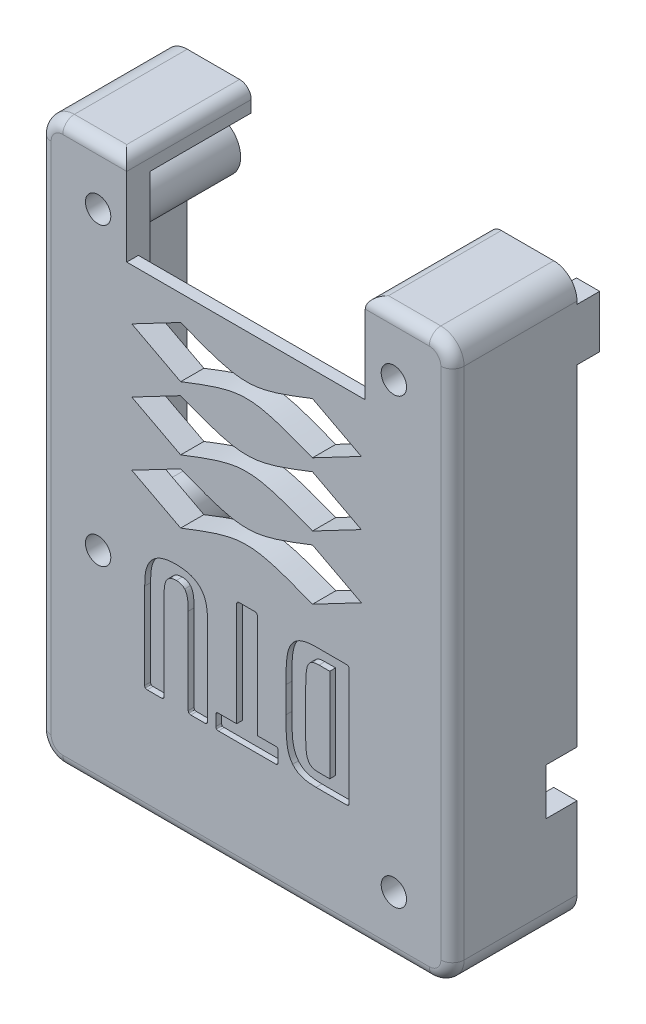
SolidWorks part; units mm, degrees
ref_plane "Front Plane" through (0, 0, 0) normal (0, 0, 1) x (1, 0, 0)
ref_plane "Top Plane" through (0, 0, 0) normal (0, 1, 0) x (1, 0, 0)
ref_plane "Right Plane" through (0, 0, 0) normal (1, 0, 0) x (0, 0, -1)
sketch "Sketch1" plane through (0, 0, 0) normal (0, 0, 1) x (1, 0, 0)
  line L1 (-7.3177, 13.3633) -> (23.1823, 13.3633)
  line L2 (-7.3177, 13.3633) -> (-7.3177, -29.8367)
  line L3 (-7.3177, -29.8367) -> (23.1823, -29.8367)
  line L4 (23.1823, 13.3633) -> (23.1823, -29.8367)
  line L5 (-7.8177, 13.8633) -> (23.6823, 13.8633)
  line L6 (-7.8177, 13.8633) -> (-7.8177, -30.3367)
  line L7 (-7.8177, -30.3367) -> (23.6823, -30.3367)
  line L8 (23.6823, 13.8633) -> (23.6823, -30.3367)
  line L9 (-9.8177, 15.8633) -> (25.6823, 15.8633)
  line L10 (-9.8177, 15.8633) -> (-9.8177, -32.3367)
  line L11 (-9.8177, -32.3367) -> (25.6823, -32.3367)
  line L12 (25.6823, 15.8633) -> (25.6823, -32.3367)
  circle A4 centre (20.6423, 10.8233) radius 1.09
  circle A6 centre (20.6423, -27.2967) radius 1.09
  circle A7 centre (-4.7777, -14.5767) radius 1.09
  circle A8 centre (-4.7777, 10.8233) radius 1.09
  dimension "D3" = 2.18
  dimension "D4" = 2.18
  dimension "D5" = 2.18
  dimension "D6" = 2.18
  dimension "D1" = 43.2
  dimension "D2" = 30.5
  dimension "D7" = 2.54
  dimension "D8" = 2.54
  dimension "D9" = 2.54
  dimension "D10" = 2.54
  dimension "D11" = 25.4
  dimension "D12" = 2.54
  dimension "D13" = 2.54
  dimension "D14" = 2.54
  dimension "D15" = 0.5
  dimension "D16" = 0.5
  dimension "D17" = 0.5
  dimension "D18" = 0.5
  dimension "D19" = 2
  dimension "D20" = 2
  dimension "D21" = 2
  dimension "D22" = 2
extrude "Boss-Extrude1" add sketch "Sketch1" along normal blind 10.7 contours A8 | A7 | A6 | L9 L12 L11 L10 | A4 region at (20.6423, -27.2967, 0) region at (-4.7777, -14.5767, 0) region at (-4.7777, 10.8233, 0)
extrude "Cut-Extrude1" cut sketch "Sketch1<6>" along normal blind 8.7 contours L6 L7 L8 L5
sketch "Sketch1<6>" plane through (0, 0, 0) normal (0, 0, 1) x (1, 0, 0) same geometry as "Sketch1"
sketch "Sketch3" plane through (-9.8177, -6.6544, 0) normal (-1, 0, 0) x (0, -1, 0)
  line L7 (-22.5177, 0) -> (25.6823, 0) construction
  line L8 (21.0823, 0) -> (10.0823, 0)
  line L9 (21.0823, 0) -> (21.0823, 4.2415)
  line L10 (21.0823, 4.2415) -> (10.0823, 4.2415)
  line L11 (10.0823, 0) -> (10.0823, 4.2415)
  line L12 (25.6823, 10.7) -> (25.6823, 0) construction
  dimension "D1" = 4.6
  dimension "D2" = 11
extrude "Cut-Extrude2" cut sketch "Sketch3" against normal blind 5
sketch "Sketch4" plane through (0, 15.8633, 0) normal (0, 1, 0) x (1, 0, 0)
  line L0 (-9.8177, 0) -> (25.6823, 0) construction
  line L1 (-2.3177, 0) -> (18.1823, 0)
  line L2 (-2.3177, 0) -> (-2.3177, -10.7)
  line L3 (-2.3177, -10.7) -> (18.1823, -10.7)
  line L4 (18.1823, 0) -> (18.1823, -10.7)
  line L5 (-9.8177, -10.7) -> (-9.8177, 0) construction
  line L6 (25.6823, -10.7) -> (25.6823, 0) construction
  dimension "D1" = 10.7
  dimension "D2" = 7.5
  dimension "D3" = 7.5
extrude "Cut-Extrude3" cut sketch "Sketch4" against normal blind 7.75
sketch "Sketch5" plane through (0, 0, 8.7) normal (0, 0, -1) x (-1, 0, 0)
  line L0 (4.7777, -12.3267) -> (7.8177, -12.3267)
  line L1 (4.7777, 13.0733) -> (7.8177, 13.0733)
  line L2 (7.8177, 13.8633) -> (7.8177, -30.3367) construction
  line L3 (4.7777, -16.8267) -> (7.8177, -16.8267)
  line L4 (4.7777, 8.5733) -> (7.8177, 8.5733)
  line L5 (-20.6423, 13.0733) -> (-23.6823, 13.0733)
  line L8 (-20.6423, 8.5733) -> (-23.6823, 8.5733)
  line L11 (-20.6423, -29.5467) -> (-23.6823, -29.5467)
  line L12 (-23.6823, 13.8633) -> (-23.6823, -30.3367) construction
  line L13 (-20.6423, -25.0467) -> (-23.6823, -25.0467)
  circle A4 centre (4.7777, -14.5767) radius 2.25
  circle A5 centre (4.7777, 10.8233) radius 2.25
  circle A6 centre (-20.6423, 10.8233) radius 2.25
  circle A7 centre (-20.6423, -27.2967) radius 2.25
  circle M2 centre (4.7777, 10.8233) radius 1.09
  circle M3 centre (4.7777, -14.5767) radius 1.09
  circle M4 centre (-20.6423, -27.2967) radius 1.09
  circle M5 centre (-20.6423, 10.8233) radius 1.09
  line M7 (-23.6823, 13.8633) -> (-23.6823, -30.3367)
  line M9 (7.8177, -30.3367) -> (7.8177, 13.8633)
  dimension "D1" = 4.5
  dimension "D2" = 4.5
  dimension "D3" = 4.5
  dimension "D4" = 4.5
extrude "Boss-Extrude3" add sketch "Sketch5" along normal blind 8 contours A4 M3 | A4 L3 L0 M9 | A7 M4 | A7 L13 L11 M7 | A6 L5 L8 M7 | A6 M5 | A5 M2 | A5 L4 L1 M9 region at (-7.0822, 10.8233, 8.7) region at (-7.0822, -14.5767, 8.7) region at (-6.3237, -13.0307, 8.7) region at (-2.5913, 10.8233, 8.7) region at (22.9468, 10.8233, 8.7) region at (22.9468, -27.2967, 8.7) region at (19.0963, 12.3693, 8.7) region at (19.0963, -25.7507, 8.7)
sketch "Sketch6" plane through (0, 0, 0) normal (0, 0, -1) x (-1, 0, 0)
  line L0 (9.8177, 15.8633) -> (9.8177, -16.7367) construction
  line L10 (-23.6823, 13.8633) -> (-23.6823, -30.3367) construction
  line L11 (-23.6823, 9.1133) -> (-25.6823, 9.1133)
  line L13 (-23.6823, 9.1133) -> (-23.6823, 13.6133)
  line L14 (-23.6823, 13.6133) -> (-25.6823, 13.6133)
  line L15 (-25.6823, 9.1133) -> (-25.6823, 13.6133)
  line L16 (-25.6823, 15.8633) -> (-25.6823, -32.3367) construction
  line L17 (-18.1823, 15.8633) -> (-25.6823, 15.8633) construction
  line L18 (9.8177, 13.6133) -> (7.8177, 13.6133)
  line L19 (9.8177, 13.6133) -> (9.8177, 9.1133)
  line L20 (9.8177, 9.1133) -> (7.8177, 9.1133)
  line L21 (7.8177, 13.6133) -> (7.8177, 9.1133)
  line L22 (7.8177, 13.8633) -> (7.8177, -16.7367) construction
  line L23 (9.8177, 15.8633) -> (2.3177, 15.8633) construction
  dimension "D1" = 4.5
  dimension "D2" = 4.5
  dimension "D3" = 2.25
  dimension "D4" = 2.25
extrude "Boss-Extrude5" add sketch "Sketch6" along normal blind 1.95
sketch "Sketch7" plane through (31.1286, 28.3579, 10.7) normal (0, 0, -1) x (1, 0, 0)
  line L0 (-28.8131, 37.7273) -> (-33.0121, 35.5217)
  line L1 (-13.2819, 35.5217) -> (-17.4799, 37.7273)
  line L2 (-17.4799, 33.3191) -> (-13.2819, 35.5217)
  line L3 (-33.0121, 35.5217) -> (-28.8131, 33.3191)
  line L4 (-28.8131, 32.2782) -> (-33.0121, 30.0746)
  line L5 (-13.2819, 30.0746) -> (-17.4799, 32.2782)
  line L6 (-17.4799, 27.87) -> (-13.2819, 30.0746)
  line L7 (-33.0121, 30.0746) -> (-28.8131, 27.87)
  line L8 (-28.8131, 26.8301) -> (-33.0121, 24.6265)
  line L9 (-13.2819, 24.6265) -> (-17.4799, 26.8301)
  line L10 (-17.4799, 22.4229) -> (-13.2819, 24.6265)
  line L11 (-33.0121, 24.6265) -> (-28.8131, 22.4229)
  line L12 (-17.1713, 51.2042) -> (-14.5519, 51.2042)
  line L13 (-19.7584, 44.8552) -> (-19.7584, 47.1015)
  line L14 (-14.5519, 40.7525) -> (-17.1713, 40.7525)
  line L15 (-14.3326, 50.985) -> (-14.3326, 40.9718)
  line L16 (-15.9946, 41.9749) -> (-15.9946, 49.9828)
  line L17 (-16.9183, 41.9749) -> (-15.9946, 41.9749)
  line L18 (-18.0737, 47.2166) -> (-18.0737, 44.7401)
  line L19 (-15.9946, 49.9828) -> (-16.9183, 49.9828)
  line L20 (-31.9038, 43.5902) -> (-31.9038, 50.985)
  line L21 (-26.4984, 50.985) -> (-26.4984, 43.5902)
  line L22 (-27.941, 51.2042) -> (-26.7176, 51.2042)
  line L23 (-28.1613, 43.5922) -> (-28.1613, 50.985)
  line L24 (-30.2409, 50.985) -> (-30.2409, 43.5922)
  line L25 (-31.6845, 51.2042) -> (-30.4602, 51.2042)
  line L26 (-24, 49.8836) -> (-24, 40.9718)
  line L27 (-25.5726, 49.8836) -> (-24, 49.8836)
  line L28 (-25.7924, 50.985) -> (-25.7924, 50.1029)
  line L29 (-20.6504, 51.2042) -> (-25.5726, 51.2042)
  line L30 (-20.4301, 50.1029) -> (-20.4301, 50.985)
  line L31 (-22.2225, 49.8836) -> (-20.6504, 49.8836)
  line L32 (-22.2225, 40.9718) -> (-22.2225, 49.8836)
  line L33 (-23.7817, 40.7525) -> (-22.4418, 40.7525)
  spline S0 degree 3 poles (-17.4799, 37.7273) (-22.918, 35.612) (-23.3769, 35.612) (-28.8131, 37.7273) knots 4 4 4 4 5 5 5 5
  spline S1 degree 3 poles (-28.8131, 33.3191) (-23.3769, 35.4334) (-22.918, 35.4334) (-17.4799, 33.3191) knots 1 1 1 1 2 2 2 2
  spline S2 degree 3 poles (-17.4799, 32.2782) (-22.918, 30.1639) (-23.3769, 30.1639) (-28.8131, 32.2782) knots 4 4 4 4 5 5 5 5
  spline S3 degree 3 poles (-28.8131, 27.87) (-23.3769, 29.9853) (-22.918, 29.9853) (-17.4799, 27.87) knots 1 1 1 1 2 2 2 2
  spline S4 degree 3 poles (-17.4799, 26.8301) (-22.918, 24.7148) (-23.3769, 24.7148) (-28.8131, 26.8301) knots 4 4 4 4 5 5 5 5
  spline S5 degree 3 poles (-28.8131, 22.4229) (-23.3769, 24.5372) (-22.918, 24.5372) (-17.4799, 22.4229) knots 1 1 1 1 2 2 2 2
  spline S6 degree 3 poles (-19.1854, 50.4859) (-18.8094, 50.973) (-18.1888, 51.2042) (-17.1713, 51.2042) knots 10 10 10 10 11 11 11 11
  spline S7 degree 3 poles (-19.7584, 47.1015) (-19.7584, 48.7476) (-19.7406, 49.8211) (-19.1854, 50.4859) knots 9 9 9 9 10 10 10 10
  spline S8 degree 3 poles (-19.1854, 41.4709) (-19.7406, 42.1356) (-19.7584, 43.2092) (-19.7584, 44.8552) knots 7 7 7 7 8 8 8 8
  spline S9 degree 3 poles (-17.1713, 40.7525) (-18.1888, 40.7525) (-18.8094, 40.9837) (-19.1854, 41.4709) knots 6 6 6 6 7 7 7 7
  spline S10 degree 3 poles (-14.3902, 40.8111) (-14.4254, 40.7763) (-14.4735, 40.7525) (-14.5519, 40.7525) knots 4 4 4 4 5 5 5 5
  spline S11 degree 3 poles (-14.3326, 40.9718) (-14.3326, 40.8934) (-14.3555, 40.8458) (-14.3902, 40.8111) knots 3 3 3 3 4 4 4 4
  spline S12 degree 3 poles (-14.3902, 51.1467) (-14.3555, 51.111) (-14.3326, 51.0643) (-14.3326, 50.985) knots 1 1 1 1 2 2 2 2
  spline S13 degree 3 poles (-14.5519, 51.2042) (-14.4735, 51.2042) (-14.4254, 51.1804) (-14.3902, 51.1467) knots 0 0 0 0 1 1 1 1
  spline S14 degree 3 poles (-17.7582, 42.2666) (-17.5697, 42.0404) (-17.3261, 41.9749) (-16.9183, 41.9749) knots 5 5 5 5 6 6 6 6
  spline S15 degree 3 poles (-18.0737, 44.7401) (-18.0737, 43.3203) (-18.0489, 42.6159) (-17.7582, 42.2666) knots 4 4 4 4 5 5 5 5
  spline S16 degree 3 poles (-17.7582, 49.6901) (-18.0489, 49.3409) (-18.0737, 48.6364) (-18.0737, 47.2166) knots 2 2 2 2 3 3 3 3
  spline S17 degree 3 poles (-16.9183, 49.9828) (-17.3261, 49.9828) (-17.5697, 49.9164) (-17.7582, 49.6901) knots 1 1 1 1 2 2 2 2
  spline S18 degree 3 poles (-31.306, 41.3697) (-31.7852, 41.9263) (-31.9038, 42.591) (-31.9038, 43.5902) knots 20 20 20 20 21 21 21 21
  spline S19 degree 3 poles (-29.206, 40.6206) (-30.2354, 40.6206) (-30.8982, 40.8964) (-31.306, 41.3697) knots 19 19 19 19 20 20 20 20
  spline S20 degree 3 poles (-27.0723, 41.3687) (-27.5163, 40.8795) (-28.1885, 40.6206) (-29.206, 40.6206) knots 18 18 18 18 19 19 19 19
  spline S21 degree 3 poles (-26.4984, 43.5902) (-26.4984, 42.5137) (-26.6447, 41.839) (-27.0723, 41.3687) knots 17 17 17 17 18 18 18 18
  spline S22 degree 3 poles (-26.5569, 51.1467) (-26.5212, 51.111) (-26.4984, 51.0643) (-26.4984, 50.985) knots 15 15 15 15 16 16 16 16
  spline S23 degree 3 poles (-26.7176, 51.2042) (-26.6387, 51.2042) (-26.5906, 51.1804) (-26.5569, 51.1467) knots 14 14 14 14 15 15 15 15
  spline S24 degree 3 poles (-28.1017, 51.1467) (-28.068, 51.1804) (-28.0199, 51.2042) (-27.941, 51.2042) knots 12 12 12 12 13 13 13 13
  spline S25 degree 3 poles (-28.1613, 50.985) (-28.1613, 51.0643) (-28.137, 51.111) (-28.1017, 51.1467) knots 11 11 11 11 12 12 12 12
  spline S26 degree 3 poles (-28.4703, 42.089) (-28.2332, 42.3499) (-28.1613, 42.7935) (-28.1613, 43.5922) knots 9 9 9 9 10 10 10 10
  spline S27 degree 3 poles (-29.1847, 41.8092) (-28.8781, 41.8092) (-28.6469, 41.8945) (-28.4703, 42.089) knots 8 8 8 8 9 9 9 9
  spline S28 degree 3 poles (-29.9323, 42.087) (-29.7622, 41.9005) (-29.5211, 41.8092) (-29.1847, 41.8092) knots 7 7 7 7 8 8 8 8
  spline S29 degree 3 poles (-30.2409, 43.5922) (-30.2409, 42.8212) (-30.1823, 42.3628) (-29.9323, 42.087) knots 6 6 6 6 7 7 7 7
  spline S30 degree 3 poles (-30.2994, 51.1467) (-30.2642, 51.111) (-30.2409, 51.0643) (-30.2409, 50.985) knots 4 4 4 4 5 5 5 5
  spline S31 degree 3 poles (-30.4602, 51.2042) (-30.3818, 51.2042) (-30.3341, 51.1804) (-30.2994, 51.1467) knots 3 3 3 3 4 4 4 4
  spline S32 degree 3 poles (-31.8453, 51.1467) (-31.811, 51.1804) (-31.7624, 51.2042) (-31.6845, 51.2042) knots 1 1 1 1 2 2 2 2
  spline S33 degree 3 poles (-31.9038, 50.985) (-31.9038, 51.0643) (-31.88, 51.111) (-31.8453, 51.1467) knots 0 0 0 0 1 1 1 1
  spline S34 degree 3 poles (-25.7349, 49.9412) (-25.6996, 49.9064) (-25.6515, 49.8836) (-25.5726, 49.8836) knots 17 17 17 17 18 18 18 18
  spline S35 degree 3 poles (-25.7924, 50.1029) (-25.7924, 50.0245) (-25.7681, 49.9759) (-25.7349, 49.9412) knots 16 16 16 16 17 17 17 17
  spline S36 degree 3 poles (-25.7349, 51.1467) (-25.7681, 51.111) (-25.7924, 51.0643) (-25.7924, 50.985) knots 14 14 14 14 15 15 15 15
  spline S37 degree 3 poles (-25.5726, 51.2042) (-25.6515, 51.2042) (-25.6996, 51.1804) (-25.7349, 51.1467) knots 13 13 13 13 14 14 14 14
  spline S38 degree 3 poles (-20.4887, 51.1467) (-20.5244, 51.1804) (-20.5715, 51.2042) (-20.6504, 51.2042) knots 11 11 11 11 12 12 12 12
  spline S39 degree 3 poles (-20.4301, 50.985) (-20.4301, 51.0643) (-20.4539, 51.111) (-20.4887, 51.1467) knots 10 10 10 10 11 11 11 11
  spline S40 degree 3 poles (-20.4887, 49.9412) (-20.4539, 49.9759) (-20.4301, 50.0245) (-20.4301, 50.1029) knots 8 8 8 8 9 9 9 9
  spline S41 degree 3 poles (-20.6504, 49.8836) (-20.5715, 49.8836) (-20.5244, 49.9064) (-20.4887, 49.9412) knots 7 7 7 7 8 8 8 8
  spline S42 degree 3 poles (-22.2811, 40.8111) (-22.2453, 40.8458) (-22.2225, 40.8934) (-22.2225, 40.9718) knots 4 4 4 4 5 5 5 5
  spline S43 degree 3 poles (-22.4418, 40.7525) (-22.3639, 40.7525) (-22.3153, 40.7763) (-22.2811, 40.8111) knots 3 3 3 3 4 4 4 4
  spline S44 degree 3 poles (-23.9425, 40.8111) (-23.9073, 40.7763) (-23.8596, 40.7525) (-23.7817, 40.7525) knots 1 1 1 1 2 2 2 2
  spline S45 degree 3 poles (-24, 40.9718) (-24, 40.8934) (-23.9772, 40.8458) (-23.9425, 40.8111) knots 0 0 0 0 1 1 1 1
extrude "Cut-Extrude5" cut sketch "Sketch7" along normal blind 0.5
extrude "Cut-Extrude10" cut sketch "Sketch7<3>" along normal blind 10 contours S1 L3 L0 S0 L1 L2 | S3 L7 L4 S2 L5 L6 | S5 L11 L8 S4 L9 L10 region at (7.9818, -7.165, 10.7) region at (7.9818, -1.7163, 10.7) region at (7.9818, 3.7315, 10.7)
sketch "Sketch7<3>" plane through (31.1286, 28.3579, 10.7) normal (0, 0, -1) x (1, 0, 0) same geometry as "Sketch7"
sketch "Sketch8" plane through (25.6823, 0, 0) normal (1, 0, 0) x (0, 0, -1)
  line L0 (0, 9.1133) -> (0, -32.3367) construction
  line L1 (0, -23.3367) -> (-2.6493, -23.3367)
  line L2 (0, -23.3367) -> (0, -19.3367)
  line L3 (0, -19.3367) -> (-2.6493, -19.3367)
  line L4 (-2.6493, -23.3367) -> (-2.6493, -19.3367)
  line L5 (-10.7, -32.3367) -> (0, -32.3367) construction
  dimension "D1" = 9
  dimension "D2" = 4
extrude "Cut-Extrude6" cut sketch "Sketch8" against normal blind 10
fillet "Fillet1" radius 2 6 edges at (-9.8177, 15.8633, 5.35) (25.6823, 15.8633, 5.35) (-9.8177, -32.3367, 5.35) (25.6823, -32.3367, 5.35) (-8.8177, -27.7367, 4.2415) (-8.8177, -16.7367, 4.2415)
fillet "Fillet2" radius 1 11 edges at (-9.2319, 15.2775, 10.7) (-9.8177, -8.2367, 10.7) (-9.2319, -31.7509, 10.7) (7.9323, -32.3367, 10.7) (25.0965, -31.7509, 10.7) (25.6823, -8.2367, 10.7) (25.0965, 15.2775, 10.7) (-5.0677, 15.8633, 10.7) (20.9323, 15.8633, 10.7) (18.1823, 15.8633, 5.35) (-2.3177, 15.8633, 5.35)
fillet "Fillet3" radius 1 5 edges at (-9.8177, -16.7367, 1.1207) (-9.8177, -17.3225, 3.6557) (-9.8177, -22.2367, 4.2415) (-9.8177, -27.7367, 1.1207) (-9.8177, -27.1509, 3.6557)
chamfer "Chamfer1" distance 1 angle 45 1 edges at (7.9323, 8.1133, 8.7)
